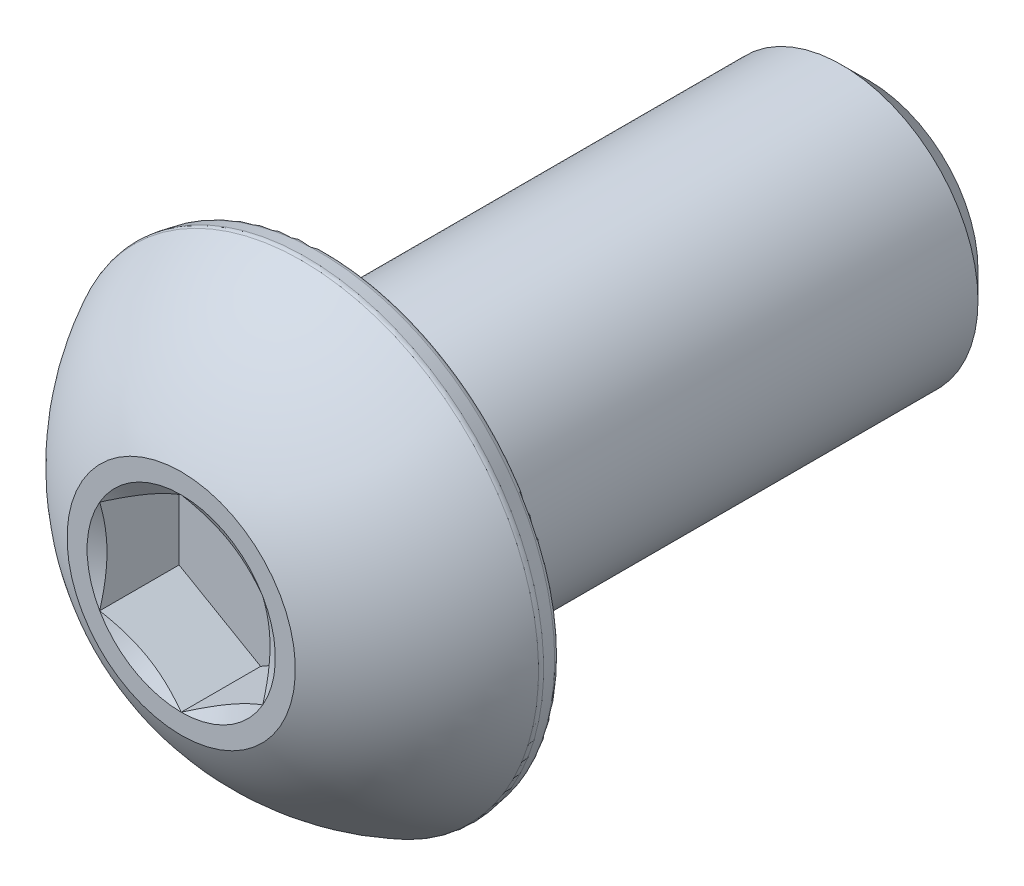
SolidWorks part; units mm, degrees
ref_plane "Front Plane" through (0, 0, 0) normal (0, 0, 1) x (1, 0, 0)
ref_plane "Top Plane" through (0, 0, 0) normal (0, 1, 0) x (1, 0, 0)
ref_plane "Right Plane" through (0, 0, 0) normal (1, 0, 0) x (0, 0, -1)
sketch "Sketch1" plane through (0, 0, 0) normal (1, 0, 0) x (0, 0, -1)
  line L0 (-10.0457, 0) -> (10.0457, 0) construction
  line L1 (-10.0457, 0) -> (-10.0457, 6.9469)
  line L2 (-10.0457, 6.9469) -> (-5.8293, 6.9469)
  line L3 (-5.8293, 6.9469) -> (-5.8293, 3.9751)
  line L4 (-5.8293, 3.9751) -> (10.0457, 3.9751)
  line L5 (10.0457, 3.9751) -> (10.0457, 0)
  point P2 (0, 0)
  point P4 (8.9874, 0)
  point P9 (8.4582, 3.9751)
  point P10 (8.4582, -3.9751)
  point P11 (10.0457, -3.9751)
  point P15 (-7.7267, 0)
  dimension "Head Height" = 4.2164
  dimension "Head Diameter" = 13.8938
  dimension "Length" = 15.875
  dimension "Screw Size Decimal Equivalent" = 7.9502
  dimension "Thread Pitch" = 1.0583
  dimension "D1" = 1.5875
  dimension "D2" = 2.319
sketch "Sketch2" plane through (0, 0, 0) normal (0, 0, 1) x (1, 0, 0)
  line L0 (0, 3.9751) -> (0, 0) construction
  line L1 (0, 2.7496) -> (-2.3813, 1.3748)
  line L2 (-2.3813, 1.3748) -> (-2.3812, -1.3748)
  line L3 (-2.3812, -1.3748) -> (0, -2.7496)
  line L4 (0, -2.7496) -> (2.3813, -1.3748)
  line L5 (2.3813, -1.3748) -> (2.3813, 1.3748)
  line L6 (2.3813, 1.3748) -> (0, 2.7496)
  circle A0 centre (0, 0) radius 2.3813 construction
  circle A1 centre (0, 0) radius 3.3337
  point P10 (0, 3.3337)
  dimension "D1" = 6.6675
  dimension "Drive Size" = 4.7625
sketch "Sketch3" plane through (0, 0, 0) normal (1, 0, 0) x (0, 0, -1)
  line L0 (-10.0457, 0) -> (-10.0457, 3.3337)
  line L1 (-10.0457, 0) -> (-10.0457, 6.9469) construction
  line L2 (-10.0457, 6.9469) -> (-5.8293, 6.9469) construction
  line L3 (-6.4618, 6.9469) -> (-5.8293, 6.8354)
  line L4 (-5.8293, 6.9469) -> (-5.8293, 3.9751) construction
  line L5 (-5.8293, 6.8354) -> (-5.8293, 3.9751)
  line L6 (-10.0457, 0) -> (10.0457, 0) construction
  line L7 (-10.0457, 0) -> (10.0457, 0)
  line L8 (10.0457, 0) -> (10.0457, 3.1813)
  line L9 (10.0457, 3.9751) -> (10.0457, 0) construction
  line L10 (10.0457, 3.1813) -> (9.2519, 3.9751)
  line L11 (-5.8293, 3.9751) -> (10.0457, 3.9751) construction
  line L12 (9.2519, 3.9751) -> (-5.8293, 3.9751)
  arc A0 (-10.0457, 3.3337) -> (-6.4618, 6.9469) centre (-3.0715, 0) cw
  dimension "D1" = 0.6325
  dimension "D2" = 10
  dimension "D3" = 45
  dimension "D4" = 0.7938
revolve "Revolve1" add sketch "Sketch3" angle 360 about L7
sketch "Sketch4" plane through (0, 0, 10.0457) normal (0, 0, 1) x (1, 0, 0)
  line L0 (-2.3812, -1.3748) -> (0, -2.7496) construction
  line L1 (-2.3813, 1.3748) -> (-2.3812, -1.3748) construction
  line L2 (0, 2.7496) -> (-2.3813, 1.3748) construction
  line L3 (2.3813, 1.3748) -> (0, 2.7496) construction
  line L4 (2.3813, -1.3748) -> (2.3813, 1.3748) construction
  line L5 (0, -2.7496) -> (2.3813, -1.3748) construction
  line L6 (-2.3812, -1.3748) -> (0, -2.7496)
  line L7 (-2.3813, 1.3748) -> (-2.3812, -1.3748)
  line L8 (0, 2.7496) -> (-2.3813, 1.3748)
  line L9 (2.3813, 1.3748) -> (0, 2.7496)
  line L10 (2.3813, -1.3748) -> (2.3813, 1.3748)
  line L11 (0, -2.7496) -> (2.3813, -1.3748)
extrude "Cut-Extrude1" cut sketch "Sketch4" against normal up to vertex (2.319 mm away) up to point (0, 0, 7.7267)
sketch "Sketch5" plane through (0, 0, 10.0457) normal (0, 0, 1) x (1, 0, 0)
  circle A0 centre (0, 0) radius 2.7496
extrude "Cut-Extrude2" cut sketch "Sketch5" against normal up to vertex (2.319 mm away) draft 60 up to point (0, 0, 7.7267)
fillet "Fillet1" radius 0.2108 2 edges at (6.9469, 0, 6.4618) (6.8354, 0, 5.8293)
split "Split1" [suppressed] bodies to split 106
sketch "Sketch6" [suppressed] plane through (0, 0, -10.0457) normal (0, 0, -1) x (-1, 0, 0)
  circle A0 centre (0, 0) radius 3.9751 construction
  circle A1 centre (0, 0) radius 3.9751
curve "Helix/Spiral1" [suppressed] pitch 1.0583 height 16.9333 turns 16
sketch "Sketch7" [suppressed] plane through (0, 0, 0) normal (1, 0, 0) x (0, 0, -1)
  line L0 (9.9796, 4.0897) -> (10.5087, 3.1731) construction
  line L1 (10.5087, 3.1731) -> (11.0379, 4.0897) construction
  line L2 (11.0379, 4.0897) -> (9.9796, 4.0897) construction
  line L3 (10.0126, 4.0324) -> (11.0048, 4.0324)
  line L4 (11.0048, 4.0324) -> (10.5749, 3.2877)
  line L5 (10.5749, 3.2877) -> (10.4426, 3.2877)
  line L6 (10.4426, 3.2877) -> (10.0126, 4.0324)
  line L7 (10.5087, 3.2877) -> (10.5087, 3.1731) construction
  line L8 (10.0457, 3.9751) -> (10.9717, 3.9751) construction
  line L9 (10.5087, 4.0897) -> (10.5087, 3.9751) construction
  point P12 (10.5087, 4.0324)
  dimension "D1" = 1.0583
  dimension "D2" = 0.1323
sweep "Cut-Sweep1" [suppressed] cut profiles "Sketch7" path "Helix/Spiral1"
sketch "Sketch8" [suppressed] plane through (0, 0, 5.8293) normal (0, 0, -1) x (-1, 0, 0)
  circle A0 centre (0, 0) radius 4.0897
extrude "Boss-Extrude1" [suppressed] add sketch "Sketch8" along normal up to vertex draft 45
equation "\"D1@Sketch1\"=\"Thread Pitch@Sketch1\"*1.5"
equation "\"D2@Sketch1\"=0.55*\"Head Height@Sketch1\""
equation "\"D1@Sketch2\"=\"Drive Size@Sketch2\"*1.4"
equation "\"D1@Sketch3\"=0.15*\"Head Height@Sketch1\""
equation "\"D4@Sketch3\"=0.75*\"Thread Pitch@Sketch1\""
equation "\"D1@Fillet1\"=.05*\"Head Height@Sketch1\""
equation "\"D4@Helix/Spiral1\"=\"Thread Pitch@Sketch1\""
equation "\"D3@Helix/Spiral1\"=\"Length@Sketch1\"+\"Thread Pitch@Sketch1\""
equation "\"D2@Sketch7\"=\"D1@Sketch7\"/8"
equation "\"D1@Sketch7\"=\"Thread Pitch@Sketch1\""
